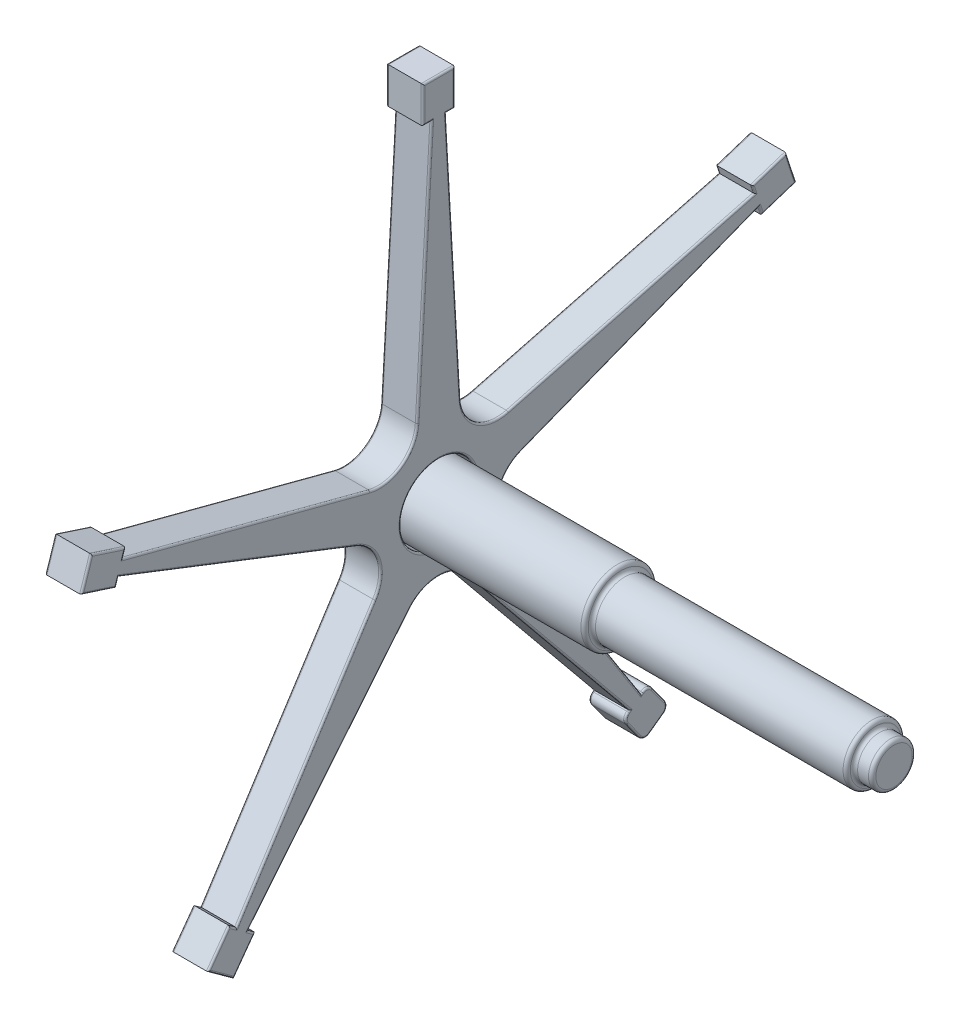
SolidWorks part; units mm, degrees
ref_plane "Front Plane" through (0, 0, 0) normal (0, 0, 1) x (1, 0, 0)
ref_plane "Top Plane" through (0, 0, 0) normal (0, 1, 0) x (1, 0, 0)
ref_plane "Right Plane" through (0, 0, 0) normal (1, 0, 0) x (0, 0, -1)
sketch "Sketch1" plane through (0, 0, 0) normal (1, 0, 0) x (0, 0, -1)
  line L0 (0, 21.8544) -> (0, 91.8544) construction
  line L1 (6, 21.8544) -> (2, 91.8544)
  line L2 (-6, 21.8544) -> (-2, 91.8544)
  line L3 (-2, 91.8544) -> (-4.3843, 91.8544)
  line L4 (18.9308, 12.4596) -> (86.7409, 30.2866)
  line L5 (22.639, 1.047) -> (87.9769, 26.4824)
  line L6 (17.6999, -14.1542) -> (55.6088, -73.1365)
  line L7 (7.9917, -21.2076) -> (52.3727, -75.4876)
  line L8 (-7.9917, -21.2076) -> (-52.3727, -75.4876)
  line L9 (-17.6999, -14.1542) -> (-55.6088, -73.1365)
  line L10 (-22.639, 1.047) -> (-87.9769, 26.4824)
  line L11 (-18.9308, 12.4596) -> (-86.7409, 30.2866)
  line L12 (-4.3843, 91.8544) -> (-4.3843, 101.8322)
  line L13 (-4.3843, 101.8322) -> (4.3843, 101.8322)
  line L14 (4.3843, 101.8322) -> (4.3843, 91.8544)
  line L15 (4.3843, 91.8544) -> (2, 91.8544)
  line L16 (-4.3843, 101.8322) -> (4.3843, 91.8544) construction
  line L17 (86.0041, 32.5542) -> (95.4935, 35.6375)
  line L18 (98.2032, 27.298) -> (88.7137, 24.2147)
  line L19 (88.7137, 24.2147) -> (87.9769, 26.4824)
  line L20 (86.7409, 30.2866) -> (86.0041, 32.5542)
  line L21 (95.4935, 35.6375) -> (98.2032, 27.298)
  line L22 (57.5378, -71.735) -> (63.4026, -79.8072)
  line L23 (56.3086, -84.9613) -> (50.4438, -76.8891)
  line L24 (50.4438, -76.8891) -> (52.3727, -75.4876)
  line L25 (55.6088, -73.1365) -> (57.5378, -71.735)
  line L26 (63.4026, -79.8072) -> (56.3086, -84.9613)
  line L27 (-50.4438, -76.8891) -> (-56.3086, -84.9613)
  line L28 (-63.4026, -79.8072) -> (-57.5378, -71.735)
  line L29 (-57.5378, -71.735) -> (-55.6088, -73.1365)
  line L30 (-52.3727, -75.4876) -> (-50.4438, -76.8891)
  line L31 (-56.3086, -84.9613) -> (-63.4026, -79.8072)
  line L32 (-88.7137, 24.2147) -> (-98.2032, 27.298)
  line L33 (-95.4935, 35.6375) -> (-86.0041, 32.5542)
  line L34 (-86.0041, 32.5542) -> (-86.7409, 30.2866)
  line L35 (-87.9769, 26.4824) -> (-88.7137, 24.2147)
  line L36 (-98.2032, 27.298) -> (-95.4935, 35.6375)
  circle A0 centre (0, 0) radius 10.5
  circle A1 centre (0, 96.8433) radius 2.7218
  arc A2 (17.6999, -14.1542) -> (22.639, 1.047) centre (26.3839, -8.5728) cw
  arc A3 (18.9308, 12.4596) -> (6, 21.8544) centre (16.3062, 22.4434) cw
  arc A4 (-6, 21.8544) -> (-18.9308, 12.4596) centre (-16.3062, 22.4434) cw
  arc A5 (-22.639, 1.047) -> (-17.6999, -14.1542) centre (-26.3839, -8.5728) cw
  arc A6 (-7.9917, -21.2076) -> (7.9917, -21.2076) centre (0, -27.7418) cw
  dimension "D9" = 9.9778
  dimension "D10" = 4.9889
  dimension "D11" = 5.4436
  dimension "D6" = 70
  dimension "D1" = 21
  dimension "D2" = 70
  dimension "D3" = 12
  dimension "D4" = 4
  dimension "D5" = 70
  dimension "D7" = 21.8544
  dimension "D8" = 2.3843
  dimension "D12" = 16.3062
extrude "Boss-Extrude7" add sketch "Sketch1" along normal mid plane 10 contours A1 | L8 A6 L7 L24 L23 L26 L22 L25 L6 A2 L5 L19 L18 L21 L17 L20 L4 A3 L1 L15 L14 L13 L12 L3 L2 A4 L11 L34 L33 L36 L32 L35 L10 A5 L9 L29 L28 L31 L27 L30 A0 A1 region at (0, 11.8991, -8.6453) region at (0, 96.8433, 0)
sketch "Sketch3" plane through (-5, 0, 0) normal (-1, 0, 0) x (0, 0, 1)
  circle A0 centre (0, 96.9302) radius 3.145
  circle A1 centre (92.1861, 29.9531) radius 3.145
  circle A2 centre (56.9742, -78.4182) radius 3.145
  circle A3 centre (-56.9742, -78.4182) radius 3.145
  circle A4 centre (-92.1861, 29.9531) radius 3.145
  point P12 (0, 0)
  dimension "D1" = 6.29
extrude "Cut-Extrude1" cut sketch "Sketch3" against normal blind 5
sketch "Sketch4" plane through (0, 0, 0) normal (0, 1, 0) x (1, 0, 0)
  line L0 (0, 0) -> (0, 10)
  line L1 (0, 0) -> (130, 0)
  line L2 (130, 0) -> (130, 6)
  line L3 (130, 6) -> (125, 6)
  line L4 (125, 6) -> (125, 8)
  line L5 (125, 8) -> (55, 8)
  line L6 (55, 8) -> (55, 10)
  line L7 (55, 10) -> (0, 10)
  dimension "D1" = 10
  dimension "D2" = 130
  dimension "D3" = 6
  dimension "D4" = 5
  dimension "D5" = 2
  dimension "D6" = 70
  dimension "D7" = 2
revolve "Revolve1" add sketch "Sketch4" angle 360 about L1
fillet "Fillet1" radius 1 5 edges at (125, 0, 6) (125, 0, 8) (55, 0, 8) (55, 0, 10) (130, 0, 6)
fillet "Fillet2" radius 0.5 87 edges at (-5, -17.4189, 0) (-5, -48.3476, -30.1822) (-5, -76.1884, -51.4082) (-5, -80.9252, -53.3762) (-5, -82.3843, -59.8556) (-5, -75.7711, -60.4702) (-5, -72.4358, -56.5733) (-5, -43.6453, -36.6544) (-5, -5.3828, -16.5662) (-5, 13.7647, -55.308) (-5, 25.3485, -88.3453) (-5, 25.7564, -93.4585) (-5, 31.4678, -96.8483) (-5, 34.0959, -90.7488) (-5, 31.4204, -86.3725) (-5, 21.3731, -52.8359) (-5, 14.0919, -10.2385) (-5, 56.8544, -4) (-5, 91.8544, -3.1922) (-5, 96.8433, -4.3843) (-5, 101.8322, 0) (-5, 96.8433, 4.3843) (-5, 91.8544, 3.1922) (-5, 56.8544, 4) (-5, 14.0919, 10.2385) (-5, 21.3731, 52.8359) (-5, 31.4204, 86.3725) (-5, 34.0959, 90.7488) (-5, 31.4678, 96.8483) (-5, 25.7564, 93.4585) (-5, 25.3485, 88.3453) (-5, 13.7647, 55.308) (-5, -5.3828, 16.5662) (-5, -43.6453, 36.6544) (-5, -72.4358, 56.5733) (-5, -75.7711, 60.4702) (-5, -82.3843, 59.8556) (-5, -80.9252, 53.3762) (-5, -76.1884, 51.4082) (-5, -48.3476, 30.1822) (-5, 0, -10.5) (-5, 96.9302, 3.145) (-5, 29.9531, 95.3311) (-5, -78.4182, 60.1192) (-5, -78.4182, -53.8292) (-5, 29.9531, -89.0411) (5, -76.1884, 51.4082) (5, -80.9252, 53.3762) (5, -82.3843, 59.8556) (5, -75.7711, 60.4702) (5, -72.4358, 56.5733) (5, -43.6453, 36.6544) (5, -5.3828, 16.5662) (5, 13.7647, 55.308) (5, 25.3485, 88.3453) (5, 25.7564, 93.4585) (5, 31.4678, 96.8483) (5, 34.0959, 90.7488) (5, 31.4204, 86.3725) (5, 21.3731, 52.8359) (5, 14.0919, 10.2385) (5, 56.8544, 4) (5, 91.8544, 3.1922) (5, 96.8433, 4.3843) (5, 101.8322, 0) (5, 96.8433, -4.3843) (5, 91.8544, -3.1922) (5, 56.8544, -4) (5, 14.0919, -10.2385) (5, 21.3731, -52.8359) (5, 31.4204, -86.3725) (5, 34.0959, -90.7488) (5, 31.4678, -96.8483) (5, 25.7564, -93.4585) (5, 25.3485, -88.3453) (5, 13.7647, -55.308) (5, -5.3828, -16.5662) (5, -43.6453, -36.6544) (5, -72.4358, -56.5733) (5, -75.7711, -60.4702) (5, -82.3843, -59.8556) (5, -80.9252, -53.3762) (5, -76.1884, -51.4082) (5, -48.3476, -30.1822) (5, -17.4189, 0) (5, -48.3476, 30.1822) (5, 0, -10.5)
fillet "Fillet3" radius 2 12 edges at (-4.8536, -84.7568, -56.341) (4.8536, -84.7568, -56.341) (-4.8536, -79.7748, -63.198) (4.8536, -79.7748, -63.198) (-4.8536, -71.9396, -57.5054) (4.8536, -71.9396, -57.5054) (-4.8536, -76.9215, -50.6483) (4.8536, -76.9215, -50.6483) (0, -76.8891, -50.4438) (0, -71.735, -57.5378) (0, -79.8072, -63.4026) (0, -84.9613, -56.3086)
